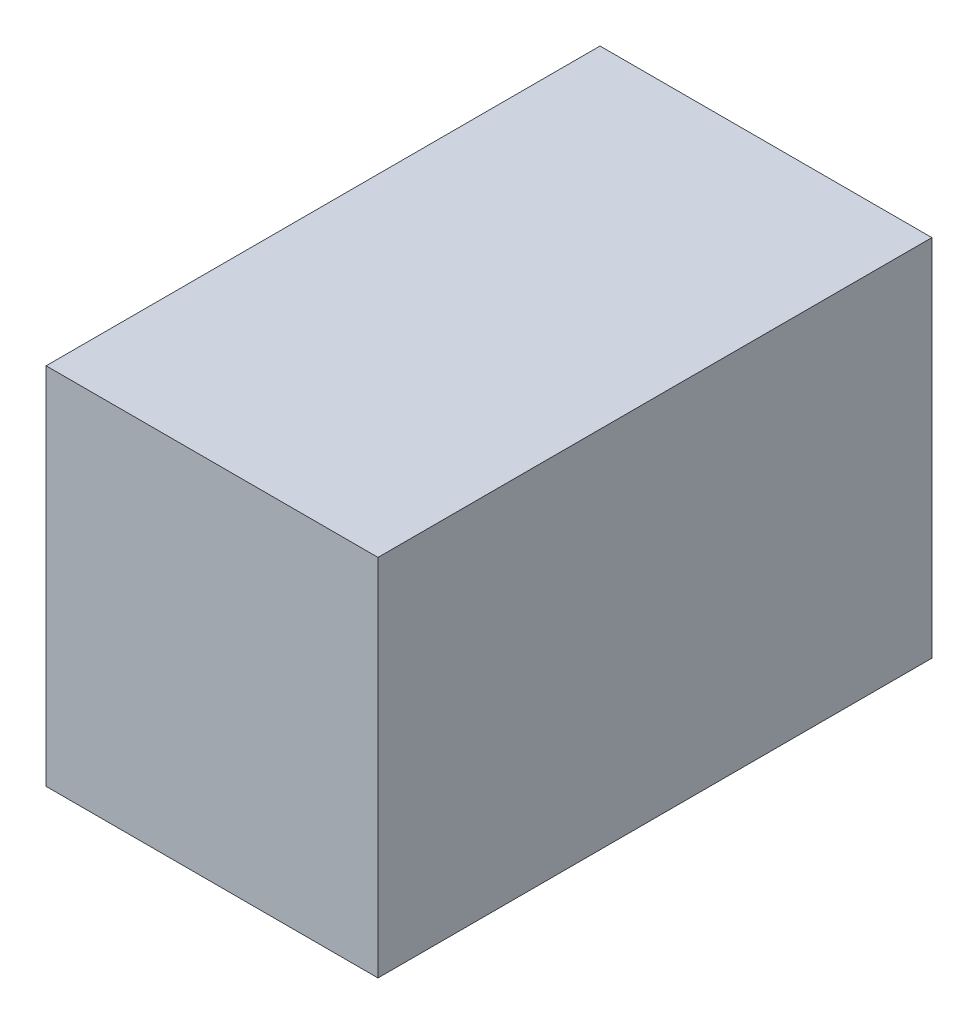
SolidWorks part; units mm, degrees
ref_plane "Front Plane" through (0, 0, 0) normal (0, 0, 1) x (1, 0, 0)
ref_plane "Top Plane" through (0, 0, 0) normal (0, 1, 0) x (1, 0, 0)
ref_plane "Right Plane" through (0, 0, 0) normal (1, 0, 0) x (0, 0, -1)
sketch "Sketch4" plane through (0, 0, 0) normal (1, 0, 0) x (0, 0, -1)
  line L1 (-15.525, 9.525) -> (15.525, 9.525)
  line L2 (-15.525, 9.525) -> (-15.525, -9.525)
  line L3 (-15.525, -9.525) -> (15.525, -9.525)
  line L4 (15.525, 9.525) -> (15.525, -9.525)
  line L5 (-15.525, 9.525) -> (15.525, -9.525) construction
  line L6 (-15.525, -9.525) -> (15.525, 9.525) construction
  point P0 (0, 0)
  dimension "D1" = 31.05
  dimension "D2" = 19.05
extrude "Boss-Extrude1" add sketch "Sketch4" along normal blind 19
shell "Shell1" thickness 2 removed face at (0, 0, 0) outward yes
sketch "Sketch5" plane through (0, 0, -17.525) normal (0, 0, -1) x (-1, 0, 0)
  line L0 (0, -11.525) -> (0, 11.525) construction
  line L1 (0, 9.525) -> (-12, 9.525)
  line L2 (-12, 9.525) -> (-12, -9.525)
  line L3 (-12, -9.525) -> (0, -9.525)
  line L4 (-21, 11.525) -> (0, 11.525) construction
  line L5 (-21, -11.525) -> (0, -11.525) construction
  line L6 (0, 9.525) -> (0, -9.525)
  dimension "D1" = 12
  dimension "D2" = 2
  dimension "D3" = 2
extrude "Cut-Extrude1" cut sketch "Sketch5" against normal up to surface (2 mm away) up to face at (9.5, 0, -15.525)
equation "\"terminalRad\"= 3mm"
equation "\"terminalLen\"= 10.5mm"
equation "\"threadlen\"=11"
